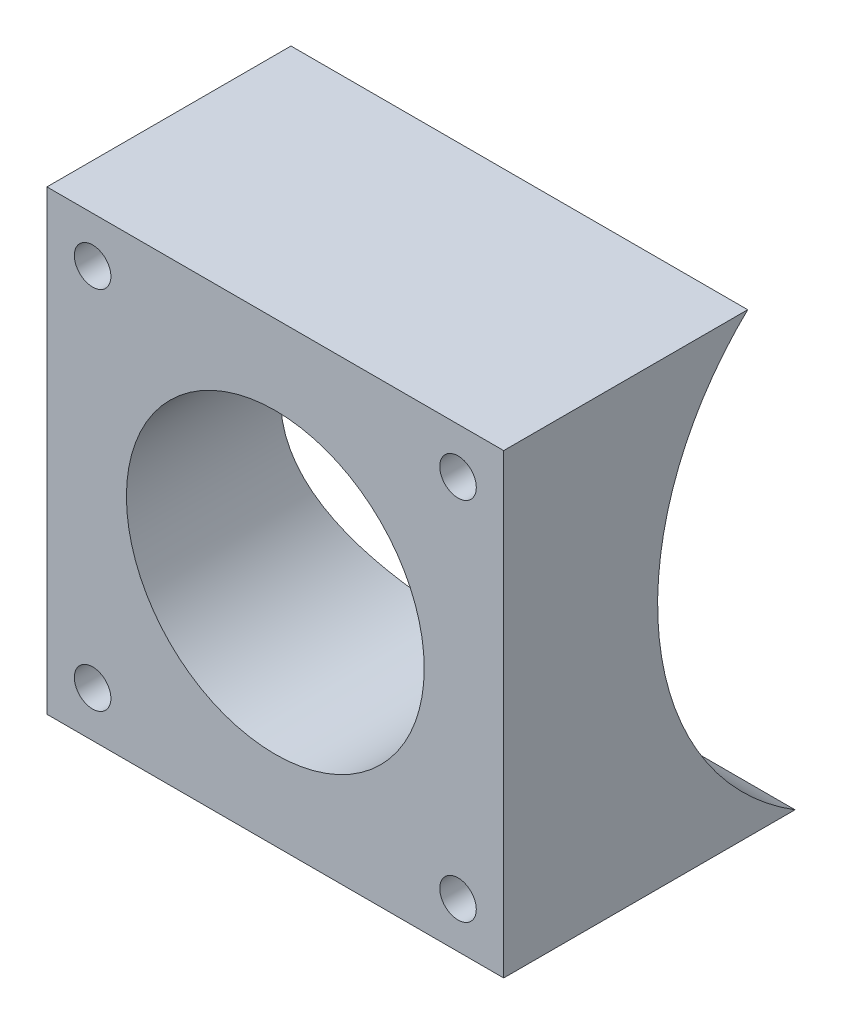
SolidWorks part; units mm, degrees
ref_plane "Front Plane" through (0, 0, 0) normal (0, 0, 1) x (1, 0, 0)
ref_plane "Top Plane" through (0, 0, 0) normal (0, 1, 0) x (1, 0, 0)
ref_plane "Right Plane" through (0, 0, 0) normal (1, 0, 0) x (0, 0, -1)
sketch "Sketch1" plane through (0, 0, 0) normal (0, 0, 1) x (1, 0, 0)
  line L1 (-25, 23) -> (25, 23)
  line L2 (-25, 23) -> (-25, -27)
  line L3 (-25, -27) -> (25, -27)
  line L4 (25, 23) -> (25, -27)
  line L5 (-25, 23) -> (25, -27) construction
  line L6 (-25, -27) -> (25, 23) construction
  circle A0 centre (0, -2) radius 16.3
  circle A1 centre (-20, 18) radius 2
  circle A2 centre (20, 18) radius 2
  circle A3 centre (20, -22) radius 2
  circle A4 centre (-20, -22) radius 2
  point P0 (0, -2)
  dimension "D4" = 32.6
  dimension "D6" = 4
  dimension "D8" = 4
  dimension "D11" = 4
  dimension "D12" = 4
  dimension "D1" = 2
  dimension "D2" = 50
  dimension "D3" = 50
  dimension "D5" = 20
  dimension "D7" = 20
  dimension "D9" = 20
  dimension "D10" = 20
extrude "Boss-Extrude1" add sketch "Sketch1" along normal blind 48.6
sketch "Sketch2" plane through (0, 0, 0) normal (1, 0, 0) x (0, 0, -1)
  circle A0 centre (0, 0) radius 31.75
  dimension "D1" = 63.5
extrude "Cut-Extrude1" cut sketch "Sketch2" against normal through all and the other way through all
